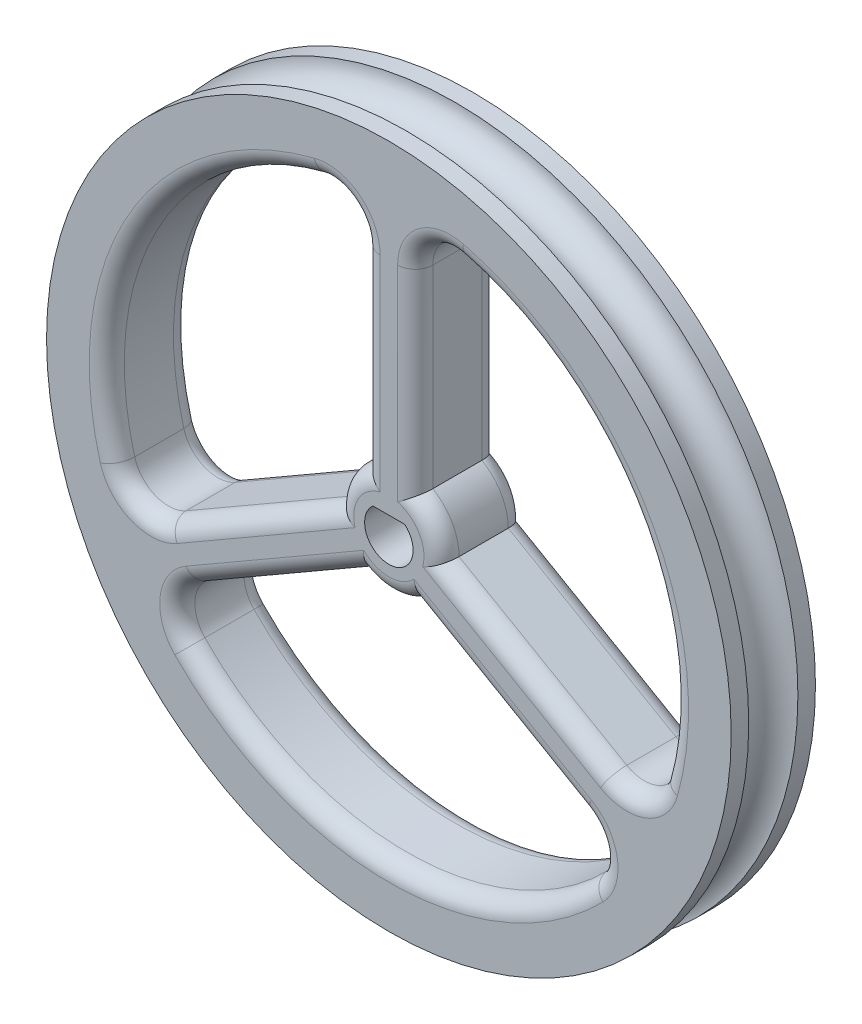
SolidWorks part; units mm, degrees
ref_plane "Front Plane" through (0, 0, 0) normal (0, 0, 1) x (1, 0, 0)
ref_plane "Top Plane" through (0, 0, 0) normal (0, 1, 0) x (1, 0, 0)
ref_plane "Right Plane" through (0, 0, 0) normal (1, 0, 0) x (0, 0, -1)
sketch "Sketch1" plane through (0, 0, 0) normal (0, 0, 1) x (1, 0, 0)
  circle A0 centre (0, 0) radius 24.765
  dimension "D1" = 49.53
extrude "Boss-Extrude1" add sketch "Sketch1" along normal blind 6.096
sketch "Sketch3" plane through (0, 0, 0) normal (1, 0, 0) x (0, 0, -1)
  line L0 (0, 24.765) -> (-6.096, 24.765) construction
  circle A0 centre (-3.048, 24.765) radius 1.778
  dimension "D1" = 3.556
ref_axis "Axis1" through (0, 0, 6.096) along (0, 0, -1)
revolve "Cut-Revolve1" cut sketch "Sketch3" angle 360 about axis through (0, 0, 6.096) along (0, 0, -1)
sketch "Sketch6" plane through (0, 0, 0) normal (0, 0, -1) x (-1, 0, 0)
  line L0 (-1.1481, 1.326) -> (1.1481, 1.326)
  line L1 (0, 0) -> (0, 30.183) construction
  line L2 (1.905, 3.2996) -> (1.905, 20.32)
  line L3 (3.81, 0) -> (18.5501, -8.5102)
  line L4 (-1.905, 3.2996) -> (-1.905, 20.32)
  line L5 (0, 0) -> (26.1392, -15.0915) construction
  line L6 (1.905, -3.2996) -> (16.6451, -11.8098)
  line L7 (-1.905, -3.2996) -> (-16.6451, -11.8098)
  line L8 (0, 0) -> (-26.1392, -15.0915) construction
  line L9 (-3.81, 0) -> (-18.5501, -8.5102)
  line L10 (-1000, -1.754) -> (49000, -1.754) construction
  arc A0 (-1.1481, 1.326) -> (1.1481, 1.326) centre (0, 0) ccw
  circle A1 centre (0, 0) radius 3.81
  circle A2 centre (0, 0) radius 20.4091
  point P9 (0, 0)
  point P24 (0, 0)
  point P26 (0, -1.754)
  dimension "D1" = 3.08
  dimension "D2" = 1.754
  dimension "D5" = 7.62
  dimension "D3" = 1.905
  dimension "D4" = 20.32
  dimension "D6" = 3
extrude "Cut-Extrude1" cut sketch "Sketch6" against normal up to next contours L4 A2 L9 A1 | L3 A2 L2 A1 | L7 A2 L6 A1 region at (-10.7648, 6.2151, 0) region at (10.7648, 6.2151, 0) region at (0, -12.4301, 0)
fillet "Fillet1" radius 2.54 6 edges at (-18.5501, -8.5102, 3.048) (-16.6451, -11.8098, 3.048) (16.6451, -11.8098, 3.048) (18.5501, -8.5102, 3.048) (-1.905, 20.32, 3.048) (1.905, 20.32, 3.048)
extrude "Cut-Extrude2" cut sketch "Sketch6<4>" against normal up to next contours L0 A0 region at (0, -0.1122, 0)
sketch "Sketch6<4>" plane through (0, 0, 0) normal (0, 0, -1) x (-1, 0, 0) same geometry as "Sketch6"
fillet "Fillet2" radius 1.27 36 edges at (-15.2827, -12.1586, 0) (-7.9706, -6.8015, 0) (0, -3.81, 0) (7.9706, -6.8015, 0) (15.2827, -12.1586, 0) (0, -20.4091, 0) (-2.8883, 19.3145, 0) (-1.905, 10.3035, 0) (-3.2996, 1.905, 0) (-9.8756, -3.502, 0) (-18.171, -7.1559, 0) (-17.6748, 10.2046, 0) (18.171, -7.1559, 0) (9.8756, -3.502, 0) (3.2996, 1.905, 0) (1.905, 10.3035, 0) (2.8883, 19.3145, 0) (17.6748, 10.2046, 0) (0, -3.81, 6.096) (-7.9706, -6.8015, 6.096) (-15.2827, -12.1586, 6.096) (0, -20.4091, 6.096) (15.2827, -12.1586, 6.096) (7.9706, -6.8015, 6.096) (-3.2996, 1.905, 6.096) (-1.905, 10.3035, 6.096) (-2.8883, 19.3145, 6.096) (-17.6748, 10.2046, 6.096) (-18.171, -7.1559, 6.096) (-9.8756, -3.502, 6.096) (3.2996, 1.905, 6.096) (9.8756, -3.502, 6.096) (18.171, -7.1559, 6.096) (17.6748, 10.2046, 6.096) (2.8883, 19.3145, 6.096) (1.905, 10.3035, 6.096)
chamfer "Chamfer1" distance 0.635 angle 45 2 edges at (0, 1.326, 0) (0, -1.754, 0)
equation "\"0.05n\"=0.1"
